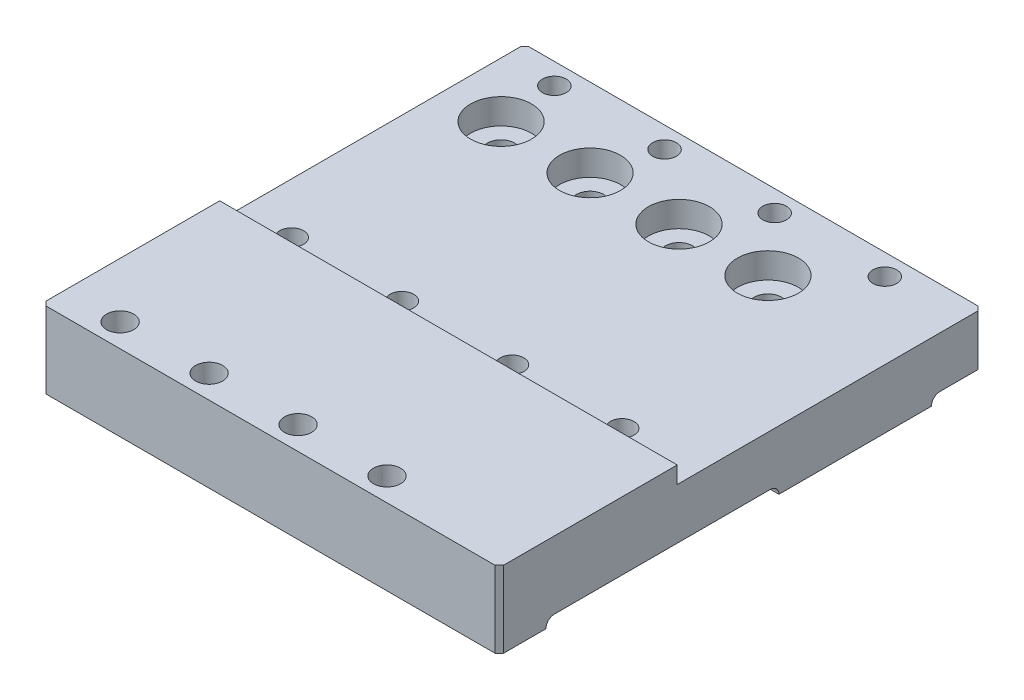
SolidWorks part; units mm, degrees
ref_plane "前视基准面" through (0, 0, 0) normal (0, 0, 1) x (1, 0, 0)
ref_plane "上视基准面" through (0, 0, 0) normal (0, 1, 0) x (1, 0, 0)
ref_plane "右视基准面" through (0, 0, 0) normal (1, 0, 0) x (0, 0, -1)
sketch "草图1" plane through (0, 0, 0) normal (0, 1, 0) x (1, 0, 0)
  line L1 (270, -285) -> (-270, -285)
  line L2 (270, -285) -> (270, 285)
  line L3 (270, 285) -> (-270, 285)
  line L4 (-270, -285) -> (-270, 285)
  line L5 (270, -285) -> (-270, 285) construction
  line L6 (270, 285) -> (-270, -285) construction
  point P0 (0, 0)
  dimension "D1" = 540
  dimension "D2" = 570
extrude "凸台-拉伸1" add sketch "草图1" against normal blind 90
sketch "草图2" plane through (-270, 0, 0) normal (-1, 0, 0) x (0, 0, 1)
  line L0 (-285, -20) -> (75, -20)
  line L1 (-285, -90) -> (-285, 0) construction
  line L2 (75, -20) -> (75, 0)
  line L3 (-285, 0) -> (285, 0) construction
  line L4 (-285, -80) -> (-225, -80)
  line L5 (-225, -80) -> (-225, -90)
  line L6 (-285, -90) -> (285, -90) construction
  line L7 (-45, -90) -> (-45, -80)
  line L8 (-45, -80) -> (230, -80)
  line L9 (230, -80) -> (230, -90)
  line L10 (285, -90) -> (285, 0) construction
  line L11 (-285, -20) -> (-285, 0)
  line L12 (-285, 0) -> (75, 0)
  line L13 (230, -90) -> (-45, -90)
  line L14 (-225, -90) -> (-285, -90)
  line L15 (-285, -90) -> (-285, -80)
  dimension "D1" = 10
  dimension "D2" = 60
  dimension "D3" = 360
  dimension "D4" = 55
  dimension "D5" = 275
  dimension "D6" = 180
extrude "切除-拉伸1" cut sketch "草图2" against normal up to next
hole_wizard "M30x2.0 螺纹孔1" positions "3D草图1" profile "草图4" tap size "M30x2.0" standard "GB" end condition up to next
sketch3d "3D草图1"
  line L0 (270, -20, 75) -> (-270, -20, 75) construction
  line L1 (270, -20, -285) -> (270, -20, 75) construction
  point P0 (180, -20, 50)
  dimension "D1" = 25
  dimension "D2" = 90
sketch "草图4" plane through (180, -20, 50) normal (1, 0, 0) x (0, 0, 1)
  line L0 (0, 0) -> (0, 60.001)
  line L1 (0, 60.001) -> (14, 60.001)
  line L2 (14, 60.001) -> (14, 0)
  line L5 (14, 0) -> (0, 0)
  line L11 (0, -6.35) -> (0, 107.95) construction
  dimension "通孔螺纹孔钻头直径" = 28
  dimension "通孔螺纹孔钻头深度" = 60.001
cosmetic thread "孔螺蚊线1" parameters "D2"=30
pattern_linear "阵列(线性)1" count 4 spacing 130 along (-1, 0, 0) count 2 spacing 310 along (0, 0, -1) of "M30x2.0 螺纹孔1"
hole_wizard "M1.6 六角头螺栓的柱形沉头孔1" positions "3D草图2" profile "草图5" counterbore size "M1.6" standard "GB" end condition up to next
sketch3d "3D草图2"
  line L0 (-270, 0, 285) -> (270, 0, 285) construction
  line L1 (-270, -20, -285) -> (-270, -20, 75) construction
  point P0 (-205, -20, -192.081)
  dimension "D1" = 477.5
  dimension "D2" = 65
sketch "草图5" plane through (-205, -20, -192.081) normal (1, 0, 0) x (0, 0, 1)
  line L0 (0, 0) -> (0, 70.001)
  line L1 (0, 70.001) -> (16, 70.001)
  line L3 (16, 70.001) -> (16, 30)
  line L4 (16, 30) -> (36, 30)
  line L5 (36, 30) -> (36, 0)
  line L7 (36, 0) -> (0, 0)
  line L11 (0, -6.35) -> (0, 107.95) construction
  dimension "通孔孔直径" = 32
  dimension "通孔孔深度" = 70.001
  dimension "柱形沉头孔直径" = 72
  dimension "柱形沉头孔深度" = 30
pattern_linear "阵列(线性)2" count 4 spacing 105 along (1, 0, 0) of "M1.6 六角头螺栓的柱形沉头孔1"
hole_wizard "Ø1.0 (1) 直径孔1" positions "3D草图3" profile "草图6" hole size "Ø1.0" standard "GB" end condition up to next
sketch3d "3D草图3"
  line L0 (-270, 0, 285) -> (270, 0, 285) construction
  line L1 (-270, 0, 75) -> (-270, 0, 285) construction
  point P0 (-205, 0, 257.5)
  dimension "D1" = 27.5
  dimension "D2" = 65
sketch "草图6" plane through (-205, 0, 257.5) normal (1, 0, 0) x (0, 0, 1)
  line L0 (0, 0) -> (0, 90.001)
  line L1 (0, 90.001) -> (16, 90.001)
  line L2 (16, 90.001) -> (16, 0)
  line L5 (16, 0) -> (0, 0)
  line L11 (0, -6.35) -> (0, 107.95) construction
  dimension "通孔孔直径" = 32
  dimension "通孔孔深度" = 90.001
pattern_linear "阵列(线性)3" count 4 spacing 105 along (1, 0, 0) of "Ø1.0 (1) 直径孔1"
ref_plane "基准面1" through (500, 0, 0) normal (1, 0, 0) x (0, 0, -1)
fillet "圆角1" radius 10 3 edges at (0, -80, -45) (0, -80, 230) (0, -80, -225)
hole_wizard "M16 螺纹孔1" positions "3D草图5" profile "草图10" tap size "M16" standard "GB"
sketch3d "3D草图5"
  line L0 (270, -80, -285) -> (-270, -80, -285) construction
  line L1 (-270, -80, -285) -> (-270, -20, -285) construction
  point P0 (-150, -48, -285)
  point P7 (150, -48, -285)
  point P10 (0, 0, 0)
  dimension "D1" = 32
  dimension "D2" = 120
  dimension "D3" = 300
sketch "草图10" plane through (-150, -48, -285) normal (1, 0, 0) x (0, 1, 0)
  line L0 (0, 0) -> (0, 34.206)
  line L1 (0, 34.206) -> (7, 30)
  line L2 (7, 30) -> (7, 0)
  line L5 (7, 0) -> (0, 0)
  line L10 (0, 34.206) -> (-7, 30) construction
  line L11 (0, -6.35) -> (0, 107.95) construction
  dimension "螺纹孔钻头直径" = 14
  dimension "螺纹孔钻头深度" = 30
  dimension "导头角度" = 118
cosmetic thread "孔螺蚊线2" parameters "D1"=20, "D2"=16
cosmetic thread "孔螺蚊线3" parameters "D1"=20, "D2"=16
chamfer "倒角1" distance 5 4 edges at (-270, -50, -285) (-270, -45, 285) (270, -45, 285) (270, -50, -285)
